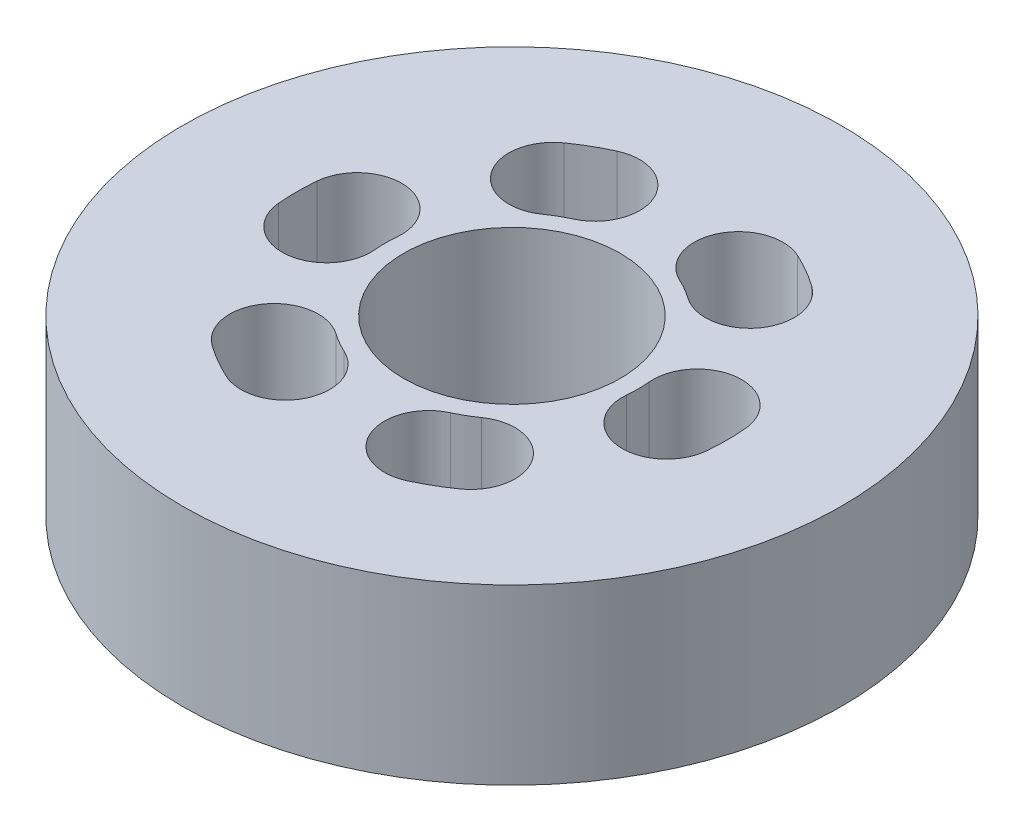
SolidWorks part; units mm, degrees
material "6061-T6 (SS)"
ref_plane "Front Plane" through (0, 0, 0) normal (0, 0, 1) x (1, 0, 0)
ref_plane "Top Plane" through (0, 0, 0) normal (0, 1, 0) x (1, 0, 0)
ref_plane "Right Plane" through (0, 0, 0) normal (1, 0, 0) x (0, 0, -1)
sketch "Sketch1" plane through (0, 0, 0) normal (0, 1, 0) x (1, 0, 0)
  circle A0 centre (0, 0) radius 24.13
  circle A1 centre (0, 0) radius 7.9375
  dimension "D1" = 48.26
  dimension "D2" = 15.875
extrude "Boss-Extrude1" add sketch "Sketch1" along normal blind 12.7
sketch "Sketch2" plane through (0, 12.7, 0) normal (0, 1, 0) x (1, 0, 0)
  line L0 (0, 0) -> (12.065, 20.8972) construction
  line L1 (0, 0) -> (0, 24.13) construction
  arc A0 (5.25, 11.3441) -> (7.1992, 10.2187) centre (0, 0) cw construction
  circle A1 centre (0, 0) radius 24.13 construction
  arc A2 (6.615, 14.2935) -> (9.071, 12.8755) centre (0, 0) cw
  arc A3 (3.885, 8.3946) -> (5.3274, 7.5618) centre (0, 0) cw
  arc A4 (6.615, 14.2935) -> (3.885, 8.3946) centre (5.25, 11.3441) ccw
  arc A5 (9.071, 12.8755) -> (5.3274, 7.5618) centre (7.1992, 10.2187) cw
  arc A6 (3.885, 8.3946) -> (5.3274, 7.5618) centre (0, 0) cw construction
  point P4 (6.25, 10.8253)
  point P22 (2, 11.3441)
  dimension "D1" = 12.5
  dimension "D5" = 2
  dimension "D2" = 30
  dimension "D3" = 3.25
  dimension "D4" = 3.25
extrude "Cut-Extrude1" cut sketch "Sketch2" against normal through all
pattern_circular "CirPattern1" count 6 over 360 about axis through (0, 12.7, 0) along (0, 1, 0) of "Cut-Extrude1"
